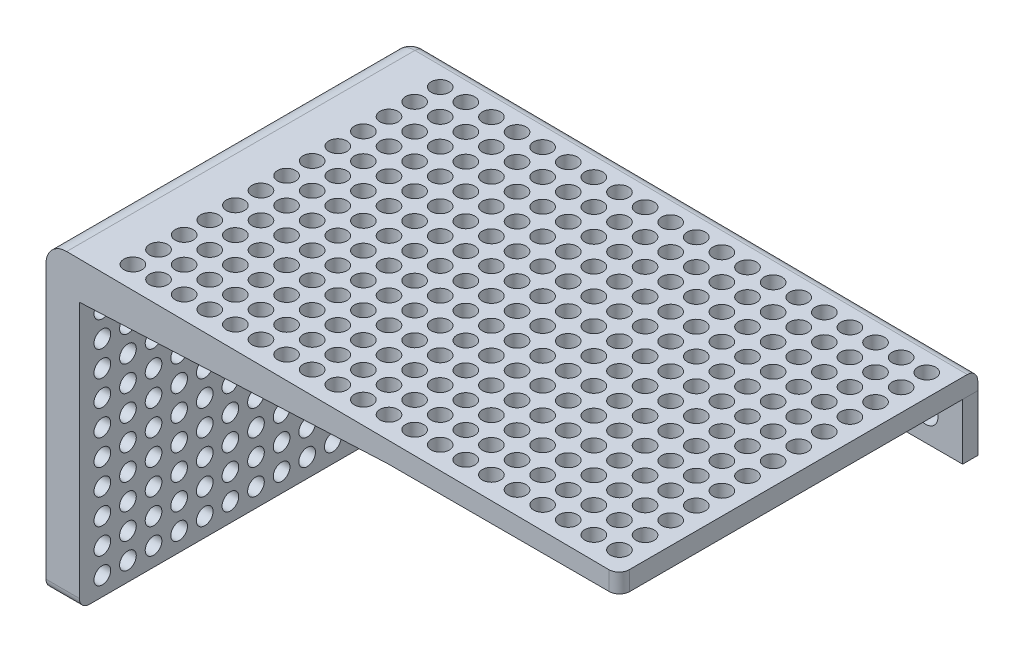
SolidWorks part; units mm, degrees
material "Custom Plastic"
ref_plane "X-Y Datum" through (0, 0, 0) normal (0, 0, 1) x (1, 0, 0)
ref_plane "X-Z Datum" through (0, 0, 0) normal (0, 1, 0) x (1, 0, 0)
ref_plane "Y-Z Datum" through (0, 0, 0) normal (1, 0, 0) x (0, 0, -1)
sketch "Sketch2" plane through (0, 0, 0) normal (0, 0, 1) x (1, 0, 0)
  line L1 (0, 0) -> (19.05, 0)
  line L2 (0, 0) -> (0, 66.1612)
  line L4 (19.05, 0) -> (19.05, 48.3812)
  line L9 (19.05, 48.3812) -> (76.5061, 55.7922)
  line L11 (76.5061, 69.7111) -> (0, 66.1612)
  line L13 (76.5061, 55.7922) -> (133.9616, 55.7922)
  line L14 (133.9616, 69.7111) -> (133.9616, 55.7922)
  line L15 (76.5061, 69.7111) -> (133.9616, 69.7111)
extrude "Boss-Extrude1" add sketch "Sketch2" along normal blind 3.81
sketch "Sketch3" plane through (0, 0, 3.81) normal (0, 0, 1) x (1, 0, 0)
  circle A0 centre (12.573, 55.5905) radius 3.048
  circle A1 centre (68.4061, 61.5595) radius 3.048
  circle A2 centre (9.525, 12.2835) radius 3.048
  circle A3 centre (124.7941, 62.8295) radius 3.048
extrude "Cut-Extrude1" cut sketch "Sketch3" against normal blind 5.08
sketch "Sketch6" plane through (0, 0, 0) normal (0, 0, -1) x (-1, 0, 0)
  line L1 (0, 0) -> (8.2523, 0)
  line L4 (8.2523, 0) -> (8.2523, 75.5146)
  line L12 (-133.8365, 74.3579) -> (-133.9616, 69.7111)
  line L16 (-133.8365, 74.3579) -> (8.2523, 75.5146)
  line L17 (-133.9616, 69.7111) -> (-76.5061, 69.7111)
  line L18 (-76.5061, 69.7111) -> (0, 66.1612)
  line L19 (0, 66.1612) -> (0, 0)
extrude "Boss-Extrude3" add sketch "Sketch6" against normal blind 88.9 separate body
sketch "Sketch11" plane through (0, 0, 3.81) normal (0, 0, 1) x (1, 0, 0)
  line L1 (19.05, 48.3812) -> (1.3157, 48.3812)
  line L2 (19.05, 48.3812) -> (19.05, 18.6329)
  line L3 (19.05, 18.6329) -> (1.3157, 18.6329)
  line L4 (1.3157, 48.3812) -> (1.3157, 18.6329)
  line L5 (19.05, 0) -> (1.3157, 0)
  line L6 (19.05, 0) -> (19.05, 6.4731)
  line L7 (19.05, 6.4731) -> (1.3157, 6.4731)
  line L8 (1.3157, 0) -> (1.3157, 6.4731)
sketch "Sketch12" plane through (0.6141, 75.4424, 0) normal (0.0081, 1, 0) x (1, -0.0081, 0)
  circle A0 centre (127.8164, -7.1776) radius 2.2513
  circle A199 centre (121.4664, -7.1776) radius 2.2513
  circle A200 centre (115.1164, -7.1776) radius 2.2513
  circle A201 centre (108.7664, -7.1776) radius 2.2513
  circle A202 centre (102.4164, -7.1776) radius 2.2513
  circle A203 centre (96.0664, -7.1776) radius 2.2513
  circle A204 centre (89.7164, -7.1776) radius 2.2513
  circle A205 centre (83.3664, -7.1776) radius 2.2513
  circle A206 centre (77.0164, -7.1776) radius 2.2513
  circle A207 centre (70.6664, -7.1776) radius 2.2513
  circle A208 centre (64.3164, -7.1776) radius 2.2513
  circle A209 centre (57.9664, -7.1776) radius 2.2513
  circle A210 centre (51.6164, -7.1776) radius 2.2513
  circle A211 centre (45.2664, -7.1776) radius 2.2513
  circle A212 centre (38.9164, -7.1776) radius 2.2513
  circle A213 centre (32.5664, -7.1776) radius 2.2513
  circle A214 centre (26.2164, -7.1776) radius 2.2513
  circle A215 centre (19.8664, -7.1776) radius 2.2513
  circle A216 centre (13.5164, -7.1776) radius 2.2513
  circle A217 centre (7.1664, -7.1776) radius 2.2513
  circle A218 centre (121.4664, -13.5276) radius 2.2513
  circle A219 centre (115.1164, -13.5276) radius 2.2513
  circle A220 centre (108.7664, -13.5276) radius 2.2513
  circle A221 centre (102.4164, -13.5276) radius 2.2513
  circle A222 centre (96.0664, -13.5276) radius 2.2513
  circle A223 centre (89.7164, -13.5276) radius 2.2513
  circle A224 centre (83.3664, -13.5276) radius 2.2513
  circle A225 centre (77.0164, -13.5276) radius 2.2513
  circle A226 centre (70.6664, -13.5276) radius 2.2513
  circle A227 centre (64.3164, -13.5276) radius 2.2513
  circle A228 centre (57.9664, -13.5276) radius 2.2513
  circle A229 centre (51.6164, -13.5276) radius 2.2513
  circle A230 centre (45.2664, -13.5276) radius 2.2513
  circle A231 centre (38.9164, -13.5276) radius 2.2513
  circle A232 centre (32.5664, -13.5276) radius 2.2513
  circle A233 centre (26.2164, -13.5276) radius 2.2513
  circle A234 centre (19.8664, -13.5276) radius 2.2513
  circle A235 centre (13.5164, -13.5276) radius 2.2513
  circle A236 centre (7.1664, -13.5276) radius 2.2513
  circle A237 centre (121.4664, -19.8776) radius 2.2513
  circle A238 centre (115.1164, -19.8776) radius 2.2513
  circle A239 centre (108.7664, -19.8776) radius 2.2513
  circle A240 centre (102.4164, -19.8776) radius 2.2513
  circle A241 centre (96.0664, -19.8776) radius 2.2513
  circle A242 centre (89.7164, -19.8776) radius 2.2513
  circle A243 centre (83.3664, -19.8776) radius 2.2513
  circle A244 centre (77.0164, -19.8776) radius 2.2513
  circle A245 centre (70.6664, -19.8776) radius 2.2513
  circle A246 centre (64.3164, -19.8776) radius 2.2513
  circle A247 centre (57.9664, -19.8776) radius 2.2513
  circle A248 centre (51.6164, -19.8776) radius 2.2513
  circle A249 centre (45.2664, -19.8776) radius 2.2513
  circle A250 centre (38.9164, -19.8776) radius 2.2513
  circle A251 centre (32.5664, -19.8776) radius 2.2513
  circle A252 centre (26.2164, -19.8776) radius 2.2513
  circle A253 centre (19.8664, -19.8776) radius 2.2513
  circle A254 centre (13.5164, -19.8776) radius 2.2513
  circle A255 centre (7.1664, -19.8776) radius 2.2513
  circle A256 centre (121.4664, -26.2276) radius 2.2513
  circle A257 centre (115.1164, -26.2276) radius 2.2513
  circle A258 centre (108.7664, -26.2276) radius 2.2513
  circle A259 centre (102.4164, -26.2276) radius 2.2513
  circle A260 centre (96.0664, -26.2276) radius 2.2513
  circle A261 centre (89.7164, -26.2276) radius 2.2513
  circle A262 centre (83.3664, -26.2276) radius 2.2513
  circle A263 centre (77.0164, -26.2276) radius 2.2513
  circle A264 centre (70.6664, -26.2276) radius 2.2513
  circle A265 centre (64.3164, -26.2276) radius 2.2513
  circle A266 centre (57.9664, -26.2276) radius 2.2513
  circle A267 centre (51.6164, -26.2276) radius 2.2513
  circle A268 centre (45.2664, -26.2276) radius 2.2513
  circle A269 centre (38.9164, -26.2276) radius 2.2513
  circle A270 centre (32.5664, -26.2276) radius 2.2513
  circle A271 centre (26.2164, -26.2276) radius 2.2513
  circle A272 centre (19.8664, -26.2276) radius 2.2513
  circle A273 centre (13.5164, -26.2276) radius 2.2513
  circle A274 centre (7.1664, -26.2276) radius 2.2513
  circle A275 centre (121.4664, -32.5776) radius 2.2513
  circle A276 centre (115.1164, -32.5776) radius 2.2513
  circle A277 centre (108.7664, -32.5776) radius 2.2513
  circle A278 centre (102.4164, -32.5776) radius 2.2513
  circle A279 centre (96.0664, -32.5776) radius 2.2513
  circle A280 centre (89.7164, -32.5776) radius 2.2513
  circle A281 centre (83.3664, -32.5776) radius 2.2513
  circle A282 centre (77.0164, -32.5776) radius 2.2513
  circle A283 centre (70.6664, -32.5776) radius 2.2513
  circle A284 centre (64.3164, -32.5776) radius 2.2513
  circle A285 centre (57.9664, -32.5776) radius 2.2513
  circle A286 centre (51.6164, -32.5776) radius 2.2513
  circle A287 centre (45.2664, -32.5776) radius 2.2513
  circle A288 centre (38.9164, -32.5776) radius 2.2513
  circle A289 centre (32.5664, -32.5776) radius 2.2513
  circle A290 centre (26.2164, -32.5776) radius 2.2513
  circle A291 centre (19.8664, -32.5776) radius 2.2513
  circle A292 centre (13.5164, -32.5776) radius 2.2513
  circle A293 centre (7.1664, -32.5776) radius 2.2513
  circle A294 centre (121.4664, -38.9276) radius 2.2513
  circle A295 centre (115.1164, -38.9276) radius 2.2513
  circle A296 centre (108.7664, -38.9276) radius 2.2513
  circle A297 centre (102.4164, -38.9276) radius 2.2513
  circle A298 centre (96.0664, -38.9276) radius 2.2513
  circle A299 centre (89.7164, -38.9276) radius 2.2513
  circle A300 centre (83.3664, -38.9276) radius 2.2513
  circle A301 centre (77.0164, -38.9276) radius 2.2513
  circle A302 centre (70.6664, -38.9276) radius 2.2513
  circle A303 centre (64.3164, -38.9276) radius 2.2513
  circle A304 centre (57.9664, -38.9276) radius 2.2513
  circle A305 centre (51.6164, -38.9276) radius 2.2513
  circle A306 centre (45.2664, -38.9276) radius 2.2513
  circle A307 centre (38.9164, -38.9276) radius 2.2513
  circle A308 centre (32.5664, -38.9276) radius 2.2513
  circle A309 centre (26.2164, -38.9276) radius 2.2513
  circle A310 centre (19.8664, -38.9276) radius 2.2513
  circle A311 centre (13.5164, -38.9276) radius 2.2513
  circle A312 centre (7.1664, -38.9276) radius 2.2513
  circle A313 centre (121.4664, -45.2776) radius 2.2513
  circle A314 centre (115.1164, -45.2776) radius 2.2513
  circle A315 centre (108.7664, -45.2776) radius 2.2513
  circle A316 centre (102.4164, -45.2776) radius 2.2513
  circle A317 centre (96.0664, -45.2776) radius 2.2513
  circle A318 centre (89.7164, -45.2776) radius 2.2513
  circle A319 centre (83.3664, -45.2776) radius 2.2513
  circle A320 centre (77.0164, -45.2776) radius 2.2513
  circle A321 centre (70.6664, -45.2776) radius 2.2513
  circle A322 centre (64.3164, -45.2776) radius 2.2513
  circle A323 centre (57.9664, -45.2776) radius 2.2513
  circle A324 centre (51.6164, -45.2776) radius 2.2513
  circle A325 centre (45.2664, -45.2776) radius 2.2513
  circle A326 centre (38.9164, -45.2776) radius 2.2513
  circle A327 centre (32.5664, -45.2776) radius 2.2513
  circle A328 centre (26.2164, -45.2776) radius 2.2513
  circle A329 centre (19.8664, -45.2776) radius 2.2513
  circle A330 centre (13.5164, -45.2776) radius 2.2513
  circle A331 centre (7.1664, -45.2776) radius 2.2513
  circle A332 centre (121.4664, -51.6276) radius 2.2513
  circle A333 centre (115.1164, -51.6276) radius 2.2513
  circle A334 centre (108.7664, -51.6276) radius 2.2513
  circle A335 centre (102.4164, -51.6276) radius 2.2513
  circle A336 centre (96.0664, -51.6276) radius 2.2513
  circle A337 centre (89.7164, -51.6276) radius 2.2513
  circle A338 centre (83.3664, -51.6276) radius 2.2513
  circle A339 centre (77.0164, -51.6276) radius 2.2513
  circle A340 centre (70.6664, -51.6276) radius 2.2513
  circle A341 centre (64.3164, -51.6276) radius 2.2513
  circle A342 centre (57.9664, -51.6276) radius 2.2513
  circle A343 centre (51.6164, -51.6276) radius 2.2513
  circle A344 centre (45.2664, -51.6276) radius 2.2513
  circle A345 centre (38.9164, -51.6276) radius 2.2513
  circle A346 centre (32.5664, -51.6276) radius 2.2513
  circle A347 centre (26.2164, -51.6276) radius 2.2513
  circle A348 centre (19.8664, -51.6276) radius 2.2513
  circle A349 centre (13.5164, -51.6276) radius 2.2513
  circle A350 centre (7.1664, -51.6276) radius 2.2513
  circle A351 centre (121.4664, -57.9776) radius 2.2513
  circle A352 centre (115.1164, -57.9776) radius 2.2513
  circle A353 centre (108.7664, -57.9776) radius 2.2513
  circle A354 centre (102.4164, -57.9776) radius 2.2513
  circle A355 centre (96.0664, -57.9776) radius 2.2513
  circle A356 centre (89.7164, -57.9776) radius 2.2513
  circle A357 centre (83.3664, -57.9776) radius 2.2513
  circle A358 centre (77.0164, -57.9776) radius 2.2513
  circle A359 centre (70.6664, -57.9776) radius 2.2513
  circle A360 centre (64.3164, -57.9776) radius 2.2513
  circle A361 centre (57.9664, -57.9776) radius 2.2513
  circle A362 centre (51.6164, -57.9776) radius 2.2513
  circle A363 centre (45.2664, -57.9776) radius 2.2513
  circle A364 centre (38.9164, -57.9776) radius 2.2513
  circle A365 centre (32.5664, -57.9776) radius 2.2513
  circle A366 centre (26.2164, -57.9776) radius 2.2513
  circle A367 centre (19.8664, -57.9776) radius 2.2513
  circle A368 centre (13.5164, -57.9776) radius 2.2513
  circle A369 centre (7.1664, -57.9776) radius 2.2513
  circle A370 centre (121.4664, -64.3276) radius 2.2513
  circle A371 centre (115.1164, -64.3276) radius 2.2513
  circle A372 centre (108.7664, -64.3276) radius 2.2513
  circle A373 centre (102.4164, -64.3276) radius 2.2513
  circle A374 centre (96.0664, -64.3276) radius 2.2513
  circle A375 centre (89.7164, -64.3276) radius 2.2513
  circle A376 centre (83.3664, -64.3276) radius 2.2513
  circle A377 centre (77.0164, -64.3276) radius 2.2513
  circle A378 centre (70.6664, -64.3276) radius 2.2513
  circle A379 centre (64.3164, -64.3276) radius 2.2513
  circle A380 centre (57.9664, -64.3276) radius 2.2513
  circle A381 centre (51.6164, -64.3276) radius 2.2513
  circle A382 centre (45.2664, -64.3276) radius 2.2513
  circle A383 centre (38.9164, -64.3276) radius 2.2513
  circle A384 centre (32.5664, -64.3276) radius 2.2513
  circle A385 centre (26.2164, -64.3276) radius 2.2513
  circle A386 centre (19.8664, -64.3276) radius 2.2513
  circle A387 centre (13.5164, -64.3276) radius 2.2513
  circle A388 centre (7.1664, -64.3276) radius 2.2513
  circle A389 centre (121.4664, -70.6776) radius 2.2513
  circle A390 centre (115.1164, -70.6776) radius 2.2513
  circle A391 centre (108.7664, -70.6776) radius 2.2513
  circle A392 centre (102.4164, -70.6776) radius 2.2513
  circle A393 centre (96.0664, -70.6776) radius 2.2513
  circle A394 centre (89.7164, -70.6776) radius 2.2513
  circle A395 centre (83.3664, -70.6776) radius 2.2513
  circle A396 centre (77.0164, -70.6776) radius 2.2513
  circle A397 centre (70.6664, -70.6776) radius 2.2513
  circle A398 centre (64.3164, -70.6776) radius 2.2513
  circle A399 centre (57.9664, -70.6776) radius 2.2513
  circle A400 centre (51.6164, -70.6776) radius 2.2513
  circle A401 centre (45.2664, -70.6776) radius 2.2513
  circle A402 centre (38.9164, -70.6776) radius 2.2513
  circle A403 centre (32.5664, -70.6776) radius 2.2513
  circle A404 centre (26.2164, -70.6776) radius 2.2513
  circle A405 centre (19.8664, -70.6776) radius 2.2513
  circle A406 centre (13.5164, -70.6776) radius 2.2513
  circle A407 centre (7.1664, -70.6776) radius 2.2513
  circle A408 centre (121.4664, -77.0276) radius 2.2513
  circle A409 centre (115.1164, -77.0276) radius 2.2513
  circle A410 centre (108.7664, -77.0276) radius 2.2513
  circle A411 centre (102.4164, -77.0276) radius 2.2513
  circle A412 centre (96.0664, -77.0276) radius 2.2513
  circle A413 centre (89.7164, -77.0276) radius 2.2513
  circle A414 centre (83.3664, -77.0276) radius 2.2513
  circle A415 centre (77.0164, -77.0276) radius 2.2513
  circle A416 centre (70.6664, -77.0276) radius 2.2513
  circle A417 centre (64.3164, -77.0276) radius 2.2513
  circle A418 centre (57.9664, -77.0276) radius 2.2513
  circle A419 centre (51.6164, -77.0276) radius 2.2513
  circle A420 centre (45.2664, -77.0276) radius 2.2513
  circle A421 centre (38.9164, -77.0276) radius 2.2513
  circle A422 centre (32.5664, -77.0276) radius 2.2513
  circle A423 centre (26.2164, -77.0276) radius 2.2513
  circle A424 centre (19.8664, -77.0276) radius 2.2513
  circle A425 centre (13.5164, -77.0276) radius 2.2513
  circle A426 centre (7.1664, -77.0276) radius 2.2513
  circle A427 centre (121.4664, -83.3776) radius 2.2513
  circle A428 centre (115.1164, -83.3776) radius 2.2513
  circle A429 centre (108.7664, -83.3776) radius 2.2513
  circle A430 centre (102.4164, -83.3776) radius 2.2513
  circle A431 centre (96.0664, -83.3776) radius 2.2513
  circle A432 centre (89.7164, -83.3776) radius 2.2513
  circle A433 centre (83.3664, -83.3776) radius 2.2513
  circle A434 centre (77.0164, -83.3776) radius 2.2513
  circle A435 centre (70.6664, -83.3776) radius 2.2513
  circle A436 centre (64.3164, -83.3776) radius 2.2513
  circle A437 centre (57.9664, -83.3776) radius 2.2513
  circle A438 centre (51.6164, -83.3776) radius 2.2513
  circle A439 centre (45.2664, -83.3776) radius 2.2513
  circle A440 centre (38.9164, -83.3776) radius 2.2513
  circle A441 centre (32.5664, -83.3776) radius 2.2513
  circle A442 centre (26.2164, -83.3776) radius 2.2513
  circle A443 centre (19.8664, -83.3776) radius 2.2513
  circle A444 centre (13.5164, -83.3776) radius 2.2513
  circle A445 centre (7.1664, -83.3776) radius 2.2513
  circle A446 centre (127.8164, -13.5276) radius 2.2513
  circle A447 centre (127.8164, -19.8776) radius 2.2513
  circle A448 centre (127.8164, -26.2276) radius 2.2513
  circle A449 centre (127.8164, -32.5776) radius 2.2513
  circle A450 centre (127.8164, -38.9276) radius 2.2513
  circle A451 centre (127.8164, -45.2776) radius 2.2513
  circle A452 centre (127.8164, -51.6276) radius 2.2513
  circle A453 centre (127.8164, -57.9776) radius 2.2513
  circle A454 centre (127.8164, -64.3276) radius 2.2513
  circle A455 centre (127.8164, -70.6776) radius 2.2513
  circle A456 centre (127.8164, -77.0276) radius 2.2513
  circle A457 centre (127.8164, -83.3776) radius 2.2513
sketch "Sketch13" plane through (-8.2523, 0, 0) normal (-1, 0, 0) x (0, 0, 1)
  circle A0 centre (6.9847, 4.6552) radius 2.0662
  circle A1 centre (13.3347, 4.6552) radius 2.0662
  circle A2 centre (19.6847, 4.6552) radius 2.0662
  circle A3 centre (26.0347, 4.6552) radius 2.0662
  circle A4 centre (32.3847, 4.6552) radius 2.0662
  circle A5 centre (38.7347, 4.6552) radius 2.0662
  circle A6 centre (45.0847, 4.6552) radius 2.0662
  circle A7 centre (51.4347, 4.6552) radius 2.0662
  circle A8 centre (57.7847, 4.6552) radius 2.0662
  circle A9 centre (64.1347, 4.6552) radius 2.0662
  circle A10 centre (70.4847, 4.6552) radius 2.0662
  circle A11 centre (76.8347, 4.6552) radius 2.0662
  circle A12 centre (83.1847, 4.6552) radius 2.0662
  circle A13 centre (13.3347, 11.0052) radius 2.0662
  circle A14 centre (19.6847, 11.0052) radius 2.0662
  circle A15 centre (26.0347, 11.0052) radius 2.0662
  circle A16 centre (32.3847, 11.0052) radius 2.0662
  circle A17 centre (38.7347, 11.0052) radius 2.0662
  circle A18 centre (45.0847, 11.0052) radius 2.0662
  circle A19 centre (51.4347, 11.0052) radius 2.0662
  circle A20 centre (57.7847, 11.0052) radius 2.0662
  circle A21 centre (64.1347, 11.0052) radius 2.0662
  circle A22 centre (70.4847, 11.0052) radius 2.0662
  circle A23 centre (76.8347, 11.0052) radius 2.0662
  circle A24 centre (83.1847, 11.0052) radius 2.0662
  circle A25 centre (13.3347, 17.3552) radius 2.0662
  circle A26 centre (19.6847, 17.3552) radius 2.0662
  circle A27 centre (26.0347, 17.3552) radius 2.0662
  circle A28 centre (32.3847, 17.3552) radius 2.0662
  circle A29 centre (38.7347, 17.3552) radius 2.0662
  circle A30 centre (45.0847, 17.3552) radius 2.0662
  circle A31 centre (51.4347, 17.3552) radius 2.0662
  circle A32 centre (57.7847, 17.3552) radius 2.0662
  circle A33 centre (64.1347, 17.3552) radius 2.0662
  circle A34 centre (70.4847, 17.3552) radius 2.0662
  circle A35 centre (76.8347, 17.3552) radius 2.0662
  circle A36 centre (83.1847, 17.3552) radius 2.0662
  circle A37 centre (13.3347, 23.7052) radius 2.0662
  circle A38 centre (19.6847, 23.7052) radius 2.0662
  circle A39 centre (26.0347, 23.7052) radius 2.0662
  circle A40 centre (32.3847, 23.7052) radius 2.0662
  circle A41 centre (38.7347, 23.7052) radius 2.0662
  circle A42 centre (45.0847, 23.7052) radius 2.0662
  circle A43 centre (51.4347, 23.7052) radius 2.0662
  circle A44 centre (57.7847, 23.7052) radius 2.0662
  circle A45 centre (64.1347, 23.7052) radius 2.0662
  circle A46 centre (70.4847, 23.7052) radius 2.0662
  circle A47 centre (76.8347, 23.7052) radius 2.0662
  circle A48 centre (83.1847, 23.7052) radius 2.0662
  circle A49 centre (13.3347, 30.0552) radius 2.0662
  circle A50 centre (19.6847, 30.0552) radius 2.0662
  circle A51 centre (26.0347, 30.0552) radius 2.0662
  circle A52 centre (32.3847, 30.0552) radius 2.0662
  circle A53 centre (38.7347, 30.0552) radius 2.0662
  circle A54 centre (45.0847, 30.0552) radius 2.0662
  circle A55 centre (51.4347, 30.0552) radius 2.0662
  circle A56 centre (57.7847, 30.0552) radius 2.0662
  circle A57 centre (64.1347, 30.0552) radius 2.0662
  circle A58 centre (70.4847, 30.0552) radius 2.0662
  circle A59 centre (76.8347, 30.0552) radius 2.0662
  circle A60 centre (83.1847, 30.0552) radius 2.0662
  circle A61 centre (13.3347, 36.4052) radius 2.0662
  circle A62 centre (19.6847, 36.4052) radius 2.0662
  circle A63 centre (26.0347, 36.4052) radius 2.0662
  circle A64 centre (32.3847, 36.4052) radius 2.0662
  circle A65 centre (38.7347, 36.4052) radius 2.0662
  circle A66 centre (45.0847, 36.4052) radius 2.0662
  circle A67 centre (51.4347, 36.4052) radius 2.0662
  circle A68 centre (57.7847, 36.4052) radius 2.0662
  circle A69 centre (64.1347, 36.4052) radius 2.0662
  circle A70 centre (70.4847, 36.4052) radius 2.0662
  circle A71 centre (76.8347, 36.4052) radius 2.0662
  circle A72 centre (83.1847, 36.4052) radius 2.0662
  circle A73 centre (13.3347, 42.7552) radius 2.0662
  circle A74 centre (19.6847, 42.7552) radius 2.0662
  circle A75 centre (26.0347, 42.7552) radius 2.0662
  circle A76 centre (32.3847, 42.7552) radius 2.0662
  circle A77 centre (38.7347, 42.7552) radius 2.0662
  circle A78 centre (45.0847, 42.7552) radius 2.0662
  circle A79 centre (51.4347, 42.7552) radius 2.0662
  circle A80 centre (57.7847, 42.7552) radius 2.0662
  circle A81 centre (64.1347, 42.7552) radius 2.0662
  circle A82 centre (70.4847, 42.7552) radius 2.0662
  circle A83 centre (76.8347, 42.7552) radius 2.0662
  circle A84 centre (83.1847, 42.7552) radius 2.0662
  circle A85 centre (13.3347, 49.1052) radius 2.0662
  circle A86 centre (19.6847, 49.1052) radius 2.0662
  circle A87 centre (26.0347, 49.1052) radius 2.0662
  circle A88 centre (32.3847, 49.1052) radius 2.0662
  circle A89 centre (38.7347, 49.1052) radius 2.0662
  circle A90 centre (45.0847, 49.1052) radius 2.0662
  circle A91 centre (51.4347, 49.1052) radius 2.0662
  circle A92 centre (57.7847, 49.1052) radius 2.0662
  circle A93 centre (64.1347, 49.1052) radius 2.0662
  circle A94 centre (70.4847, 49.1052) radius 2.0662
  circle A95 centre (76.8347, 49.1052) radius 2.0662
  circle A96 centre (83.1847, 49.1052) radius 2.0662
  circle A97 centre (13.3347, 55.4552) radius 2.0662
  circle A98 centre (19.6847, 55.4552) radius 2.0662
  circle A99 centre (26.0347, 55.4552) radius 2.0662
  circle A100 centre (32.3847, 55.4552) radius 2.0662
  circle A101 centre (38.7347, 55.4552) radius 2.0662
  circle A102 centre (45.0847, 55.4552) radius 2.0662
  circle A103 centre (51.4347, 55.4552) radius 2.0662
  circle A104 centre (57.7847, 55.4552) radius 2.0662
  circle A105 centre (64.1347, 55.4552) radius 2.0662
  circle A106 centre (70.4847, 55.4552) radius 2.0662
  circle A107 centre (76.8347, 55.4552) radius 2.0662
  circle A108 centre (83.1847, 55.4552) radius 2.0662
  circle A109 centre (13.3347, 61.8052) radius 2.0662
  circle A110 centre (19.6847, 61.8052) radius 2.0662
  circle A111 centre (26.0347, 61.8052) radius 2.0662
  circle A112 centre (32.3847, 61.8052) radius 2.0662
  circle A113 centre (38.7347, 61.8052) radius 2.0662
  circle A114 centre (45.0847, 61.8052) radius 2.0662
  circle A115 centre (51.4347, 61.8052) radius 2.0662
  circle A116 centre (57.7847, 61.8052) radius 2.0662
  circle A117 centre (64.1347, 61.8052) radius 2.0662
  circle A118 centre (70.4847, 61.8052) radius 2.0662
  circle A119 centre (76.8347, 61.8052) radius 2.0662
  circle A120 centre (83.1847, 61.8052) radius 2.0662
  circle A121 centre (6.9847, 11.0052) radius 2.0662
  circle A122 centre (6.9847, 17.3552) radius 2.0662
  circle A123 centre (6.9847, 23.7052) radius 2.0662
  circle A124 centre (6.9847, 30.0552) radius 2.0662
  circle A125 centre (6.9847, 36.4052) radius 2.0662
  circle A126 centre (6.9847, 42.7552) radius 2.0662
  circle A127 centre (6.9847, 49.1052) radius 2.0662
  circle A128 centre (6.9847, 55.4552) radius 2.0662
  circle A129 centre (6.9847, 61.8052) radius 2.0662
extrude "Cut-Extrude5" cut sketch "Sketch13" against normal blind 8.382
fillet "Fillet1" radius 5.08 1 edges at (-8.2523, 75.5146, 44.45)
extrude "Cut-Extrude6" cut sketch "Sketch11" against normal blind 8.382
fillet "Fillet2" radius 2.54 5 edges at (-8.2523, 35.1965, 0) (-6.7497, 73.9998, 0) (-4.1261, 0, 88.9) (65.3528, 74.9154, 0) (133.8991, 72.0345, 88.9)
extrude "Cut-Extrude8" cut sketch "Sketch12" against normal blind 10.668
